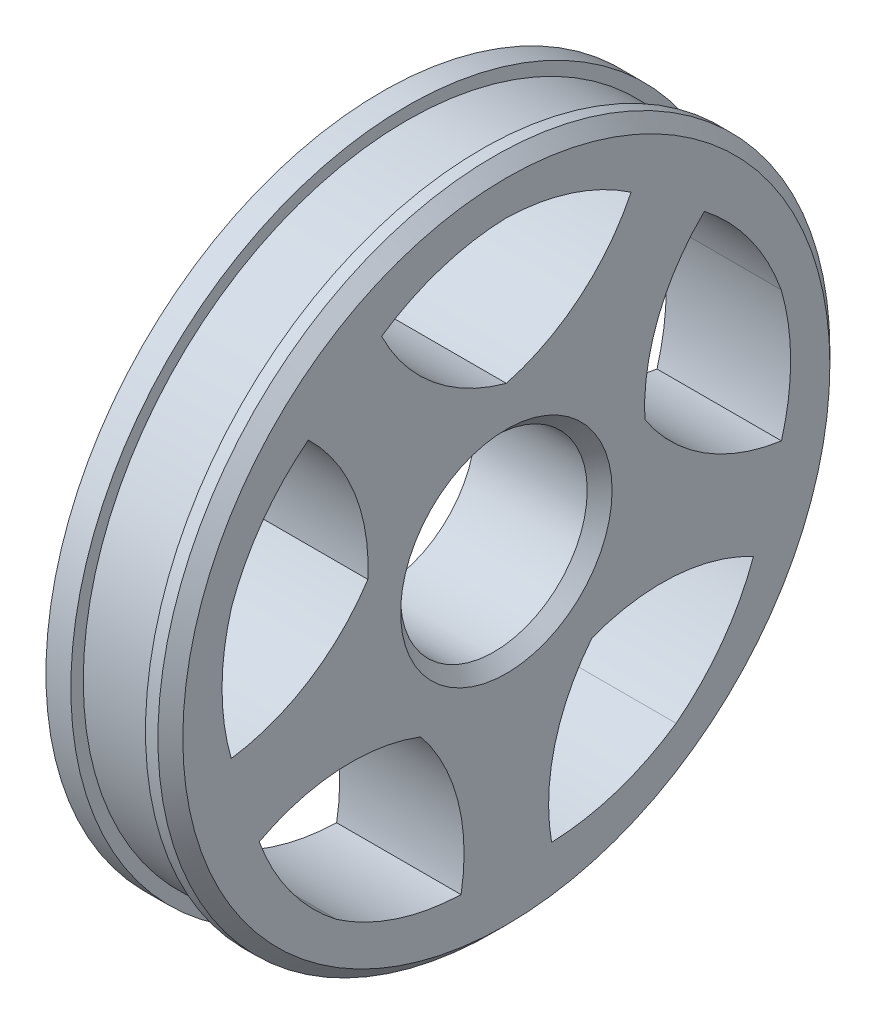
SolidWorks part; units mm, degrees
ref_plane "Front Plane" through (0, 0, 0) normal (0, 0, 1) x (1, 0, 0)
ref_plane "Top Plane" through (0, 0, 0) normal (0, 1, 0) x (1, 0, 0)
ref_plane "Right Plane" through (0, 0, 0) normal (1, 0, 0) x (0, 0, -1)
sketch "Sketch1" plane through (0, 0, 0) normal (1, 0, 0) x (0, 0, -1)
  circle A0 centre (0, 0) radius 13.5
  circle A1 centre (0, 0) radius 3.75
  dimension "D1" = 27
  dimension "D2" = 7.5
extrude "Boss-Extrude1" add sketch "Sketch1" along normal mid plane 5
sketch "Sketch2" plane through (0, 0, 0) normal (1, 0, 0) x (0, 0, -1)
  line L0 (0, 0) -> (0, 14.8201) construction
  arc A0 (0, 5.8497) -> (-5.0122, 9.994) centre (2.0377, 13.4173) cw
  arc A1 (-5.0122, 9.994) -> (0, 11.6087) centre (0.2591, 2.218) cw
  arc A2 (5.0122, 9.994) -> (0, 11.6087) centre (-0.2591, 2.218) ccw
  arc A3 (0, 5.8497) -> (5.0122, 9.994) centre (-2.0377, 13.4173) ccw
extrude "Cut-Extrude1" cut sketch "Sketch2" along normal through all both and the other way through all
pattern_circular "CirPattern1" count 5 over 360 about axis through (2.5, 0, 0) along (-1, 0, 0) of "Cut-Extrude1" reverse direction yes
chamfer "Chamfer1" distance 0.5 angle 45 2 edges at (2.5, 0, -13.5) (2.5, 0, -3.75)
sketch "Sketch4" plane through (0, 0, 0) normal (1, 0, 0) x (0, 0, -1)
  circle A0 centre (0, 0) radius 13.5
  circle A1 centre (0, 0) radius 13
  circle A2 centre (0, 0) radius 13.5 construction
  dimension "D1" = 0.5
extrude "Cut-Extrude3" cut sketch "Sketch4" against normal mid plane 3
equation "\"axis_diameter\"=5.66"
equation "\"padding\"=0.5"
